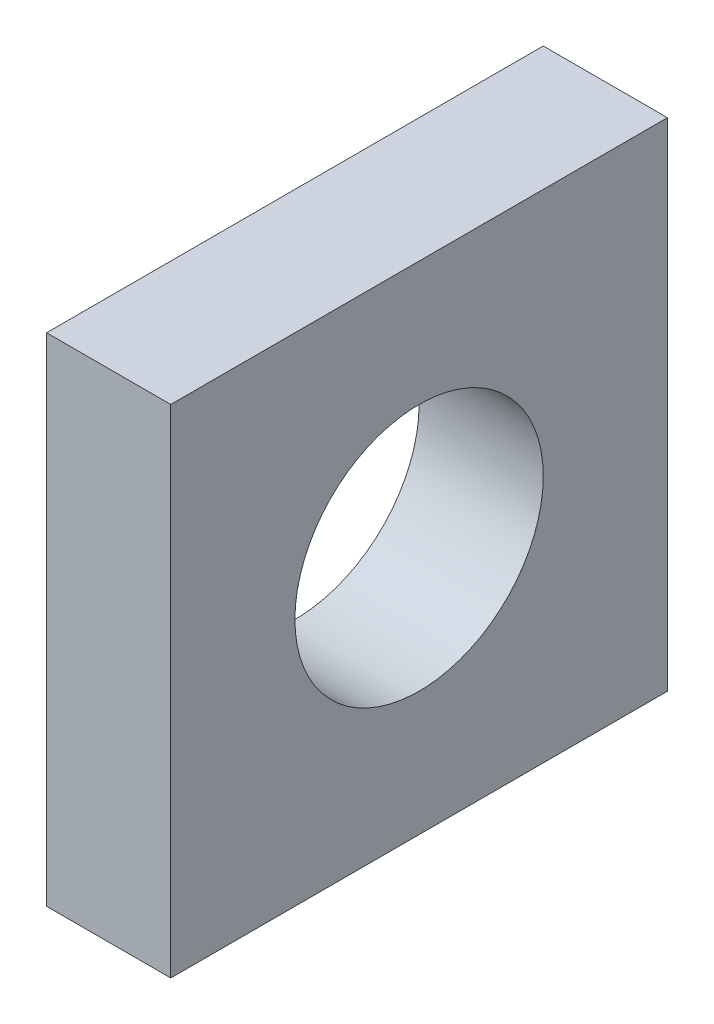
SolidWorks part; units mm, degrees
ref_plane "Front Plane" through (0, 0, 0) normal (0, 0, 1) x (1, 0, 0)
ref_plane "Top Plane" through (0, 0, 0) normal (0, 1, 0) x (1, 0, 0)
ref_plane "Right Plane" through (0, 0, 0) normal (1, 0, 0) x (0, 0, -1)
sketch "Sketch2" plane through (0, 0, 0) normal (1, 0, 0) x (0, 0, -1)
  line L1 (0, 0) -> (38.1, 0)
  line L2 (0, 0) -> (0, 38.1)
  line L3 (0, 38.1) -> (38.1, 38.1)
  line L4 (38.1, 0) -> (38.1, 38.1)
  circle A0 centre (19.05, 19.05) radius 9.525
  point P7 (0, 0)
  point P8 (0, 19.05)
  point P9 (19.05, 38.1)
  dimension "D3" = 19.05
  dimension "D1" = 38.1
  dimension "D2" = 38.1
extrude "Boss-Extrude1" add sketch "Sketch2" along normal blind 9.525
sketch "Sketch3" plane through (0, 0, -38.1) normal (0, 0, -1) x (-1, 0, 0)
  line L0 (-9.525, 0) -> (-9.525, 38.1) construction
  line L1 (-9.525, 38.1) -> (0, 38.1) construction
  line L2 (-9.525, 0) -> (0, 0) construction
  circle A0 centre (-4.7625, 34.1) radius 2
  circle A1 centre (-4.7625, 4) radius 2
  point P4 (0, 0)
  point P7 (-4.7625, 34.2771)
  dimension "D2" = 4
  dimension "D4" = 4
  dimension "D1" = 4.7625
  dimension "D3" = 4
extrude "Cut-Extrude1" cut sketch "Sketch3" against normal blind 9.525
